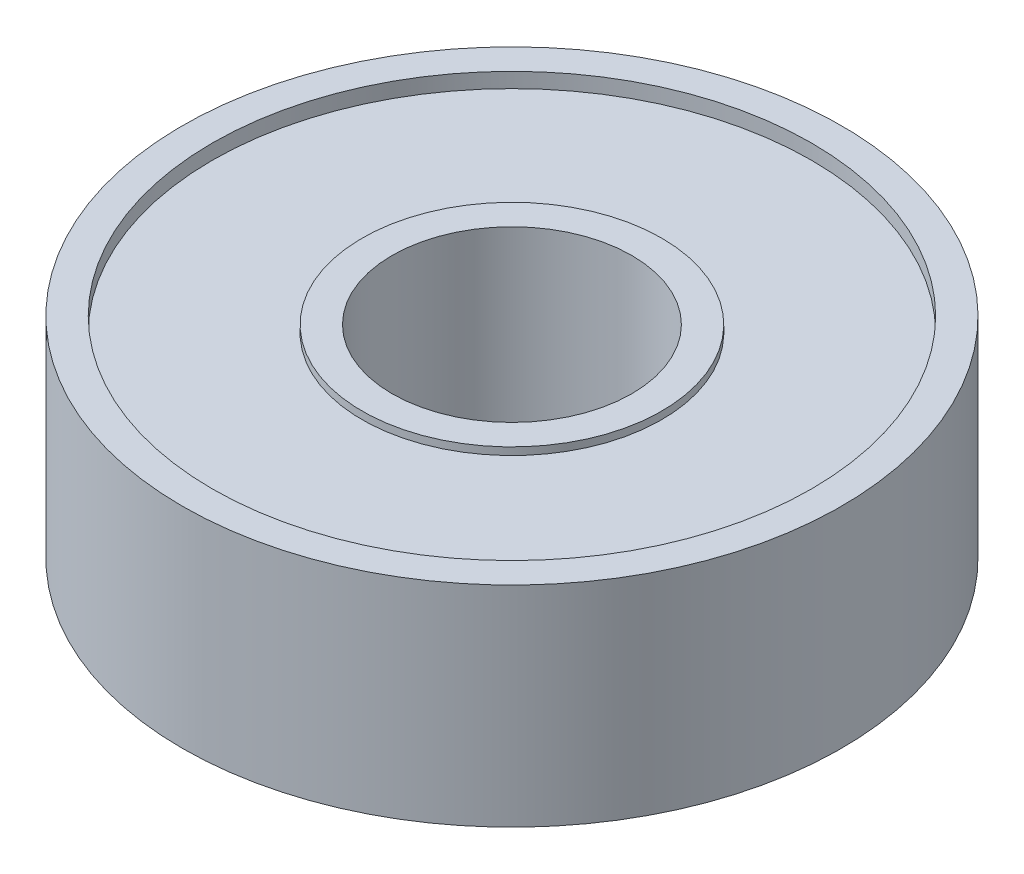
SolidWorks part; units mm, degrees
ref_plane "Front Plane" through (0, 0, 0) normal (0, 0, 1) x (1, 0, 0)
ref_plane "Top Plane" through (0, 0, 0) normal (0, 1, 0) x (1, 0, 0)
ref_plane "Right Plane" through (0, 0, 0) normal (1, 0, 0) x (0, 0, -1)
sketch "Sketch1" plane through (0, 0, 0) normal (0, 1, 0) x (1, 0, 0)
  circle A0 centre (0, 0) radius 11
  dimension "D1" = 22
extrude "Boss-Extrude1" add sketch "Sketch1" along normal mid plane 6
sketch "Sketch2" plane through (0, 0, 0) normal (0, 1, 0) x (1, 0, 0)
  circle A1 centre (0, 0) radius 11
  circle A2 centre (0, 0) radius 10
  dimension "D1" = 22
  dimension "D2" = 1
extrude "Boss-Extrude2" add sketch "Sketch2" along normal mid plane 7
sketch "Sketch4" plane through (0, 0, 0) normal (0, 1, 0) x (1, 0, 0)
  circle A0 centre (0, 0) radius 27.5915
  circle A2 centre (0, 0) radius 5
  dimension "D1" = 10
extrude "Boss-Extrude3" add sketch "Sketch4" along normal mid plane 6.5 contours A2
sketch "Sketch5" plane through (0, 3.25, 0) normal (0, 1, 0) x (1, 0, 0)
  circle A0 centre (0, 0) radius 4
  circle A2 centre (0, 0) radius 5 construction
  dimension "D1" = 1
extrude "Cut-Extrude1" cut sketch "Sketch5" against normal blind 10
